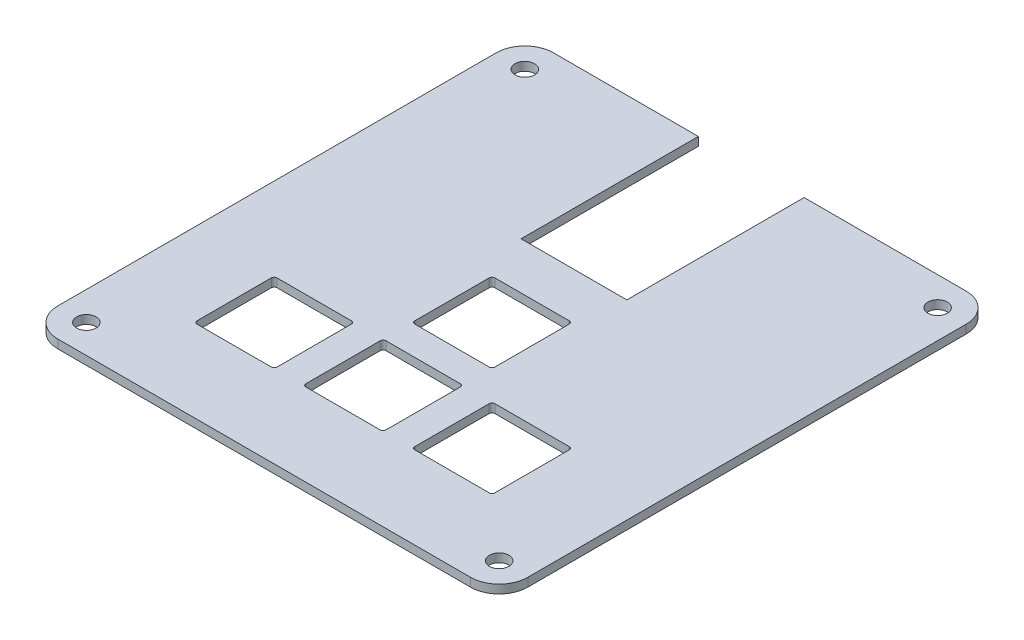
SolidWorks part; units mm, degrees
ref_plane "Front Plane" through (0, 0, 0) normal (0, 0, 1) x (1, 0, 0)
ref_plane "Top Plane" through (0, 0, 0) normal (0, 1, 0) x (1, 0, 0)
ref_plane "Right Plane" through (0, 0, 0) normal (1, 0, 0) x (0, 0, -1)
sketch "Sketch1" plane through (0, 0, 0) normal (0, 1, 0) x (1, 0, 0)
  line L0 (-6.7208, 16.4146) -> (6.2792, 16.4146)
  line L1 (-6.7208, 2.4146) -> (6.2792, 2.4146)
  line L2 (-7.2208, 15.9146) -> (-7.2208, 2.9146)
  line L3 (6.7792, 15.9146) -> (6.7792, 2.9146)
  line L4 (-25.7708, -2.6354) -> (-12.7708, -2.6354)
  line L5 (-25.7708, -16.6354) -> (-12.7708, -16.6354)
  line L6 (-26.2708, -3.1354) -> (-26.2708, -16.1354)
  line L7 (-12.2708, -3.1354) -> (-12.2708, -16.1354)
  line L8 (-6.7208, -2.6354) -> (6.2792, -2.6354)
  line L9 (-6.7208, -16.6354) -> (6.2792, -16.6354)
  line L10 (-7.2208, -3.1354) -> (-7.2208, -16.1354)
  line L11 (6.7792, -3.1354) -> (6.7792, -16.1354)
  line L12 (12.3292, -2.6354) -> (25.3292, -2.6354)
  line L13 (12.3292, -16.6354) -> (25.3292, -16.6354)
  line L14 (11.8292, -3.1354) -> (11.8292, -16.1354)
  line L15 (25.8292, -3.1354) -> (25.8292, -16.1354)
  arc A0 (-6.7208, 16.4146) -> (-7.2208, 15.9146) centre (-6.7208, 15.9146) ccw
  arc A1 (6.7792, 15.9146) -> (6.2792, 16.4146) centre (6.2792, 15.9146) ccw
  arc A2 (-7.2208, 2.9146) -> (-6.7208, 2.4146) centre (-6.7208, 2.9146) ccw
  arc A3 (6.2792, 2.4146) -> (6.7792, 2.9146) centre (6.2792, 2.9146) ccw
  arc A4 (-25.7708, -2.6354) -> (-26.2708, -3.1354) centre (-25.7708, -3.1354) ccw
  arc A5 (-12.2708, -3.1354) -> (-12.7708, -2.6354) centre (-12.7708, -3.1354) ccw
  arc A6 (-26.2708, -16.1354) -> (-25.7708, -16.6354) centre (-25.7708, -16.1354) ccw
  arc A7 (-12.7708, -16.6354) -> (-12.2708, -16.1354) centre (-12.7708, -16.1354) ccw
  arc A8 (-6.7208, -2.6354) -> (-7.2208, -3.1354) centre (-6.7208, -3.1354) ccw
  arc A9 (6.7792, -3.1354) -> (6.2792, -2.6354) centre (6.2792, -3.1354) ccw
  arc A10 (-7.2208, -16.1354) -> (-6.7208, -16.6354) centre (-6.7208, -16.1354) ccw
  arc A11 (6.2792, -16.6354) -> (6.7792, -16.1354) centre (6.2792, -16.1354) ccw
  arc A12 (12.3292, -2.6354) -> (11.8292, -3.1354) centre (12.3292, -3.1354) ccw
  arc A13 (25.8292, -3.1354) -> (25.3292, -2.6354) centre (25.3292, -3.1354) ccw
  arc A14 (11.8292, -16.1354) -> (12.3292, -16.6354) centre (12.3292, -16.1354) ccw
  arc A15 (25.3292, -16.6354) -> (25.8292, -16.1354) centre (25.3292, -16.1354) ccw
  point P0 (0, 0)
sketch "Sketch2" plane through (0, 0, 0) normal (0, 1, 0) x (1, 0, 0)
  line L1 (41.4982, 55.6236) -> (-40.6918, 55.6236)
  line L2 (41.4982, 55.6236) -> (41.4982, -31.0564)
  line L3 (41.4982, -31.0564) -> (-40.6918, -31.0564)
  line L4 (-40.6918, 55.6236) -> (-40.6918, -31.0564)
  line L5 (41.4982, 55.6236) -> (-40.6918, -31.0564) construction
  line L6 (41.4982, -31.0564) -> (-40.6918, 55.6236) construction
  line L12 (-25.7708, -16.6354) -> (-12.7708, -16.6354) construction
  line L13 (-26.2708, -3.1354) -> (-26.2708, -16.1354) construction
  line L16 (-10.3518, 55.6236) -> (8.1482, 55.6236)
  line L17 (-10.3518, 55.6236) -> (-10.3518, 24.6236)
  line L18 (-10.3518, 24.6236) -> (8.1482, 24.6236)
  line L19 (8.1482, 55.6236) -> (8.1482, 24.6236)
  circle A0 centre (36.4982, 50.6236) radius 1.7
  circle A1 centre (-35.6918, 50.6236) radius 1.7
  circle A2 centre (-35.6918, -26.0564) radius 1.7
  circle A3 centre (36.4982, -26.0564) radius 1.7
  point P0 (0, 0)
  dimension "D8" = 3.4
  dimension "D9" = 3.4
  dimension "D10" = 3.4
  dimension "D11" = 3.4
  dimension "D1" = 82.19
  dimension "D2" = 86.68
  dimension "D3" = 14.421
  dimension "D4" = 14.421
  dimension "D5" = 18.5
  dimension "D6" = 31
  dimension "D7" = 30.34
  dimension "D12" = 5
  dimension "D13" = 5
  dimension "D14" = 5
  dimension "D15" = 5
  dimension "D16" = 5
  dimension "D17" = 5
  dimension "D18" = 5
  dimension "D19" = 5
extrude "Boss-Extrude3" add sketch "Sketch2" along normal blind 1.5 contours L1 L19 L18 L17 L4 L3 L2 A3 A2 A1 A0 region at (0.5357, 0, -9.8327)
extrude "Cut-Extrude5" cut sketch "Sketch1" against normal blind 4.5 and the other way blind 7
fillet "Fillet4" radius 5 4 edges at (-40.6918, 0.75, 31.0564) (41.4982, 0.75, 31.0564) (41.4982, 0.75, -55.6236) (-40.6918, 0.75, -55.6236)
